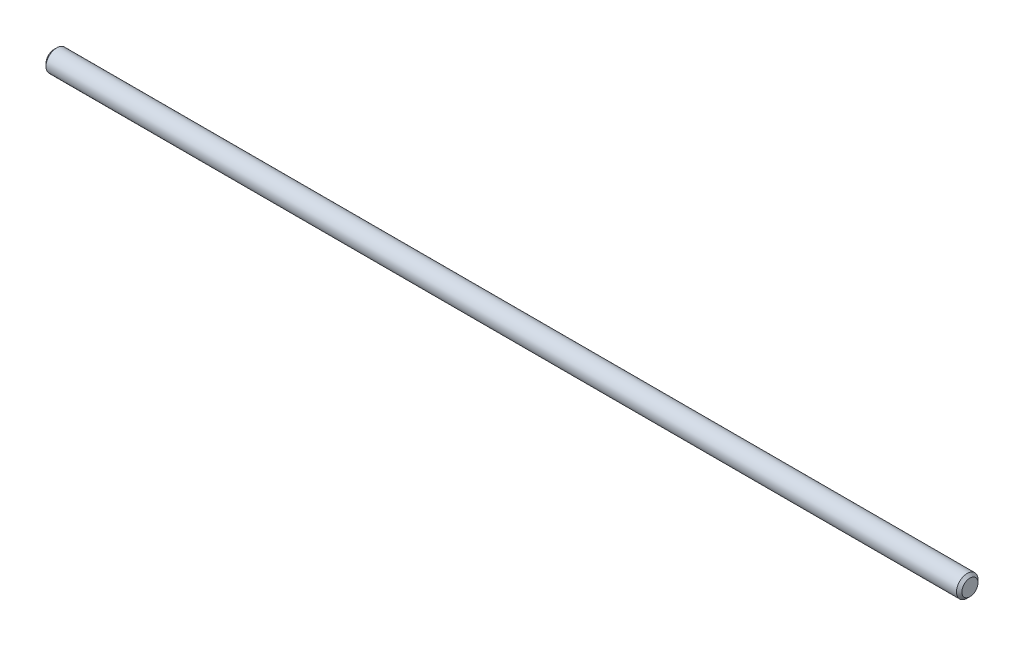
SolidWorks part; units mm, degrees
ref_plane "Alzado" through (0, 0, 0) normal (0, 0, 1) x (1, 0, 0)
ref_plane "Planta" through (0, 0, 0) normal (0, 1, 0) x (1, 0, 0)
ref_plane "Vista lateral" through (0, 0, 0) normal (1, 0, 0) x (0, 0, -1)
sketch "Croquis1" plane through (0, 0, 0) normal (1, 0, 0) x (0, 0, -1)
  circle A0 centre (0, 0) radius 4
  dimension "D1" = 8
extrude "Saliente-Extruir1" add sketch "Croquis1" along normal blind 170 and the other way blind 170
chamfer "Chaflán1" distance 1 angle 45 2 edges at (-170, 0, -4) (170, 0, -4)
